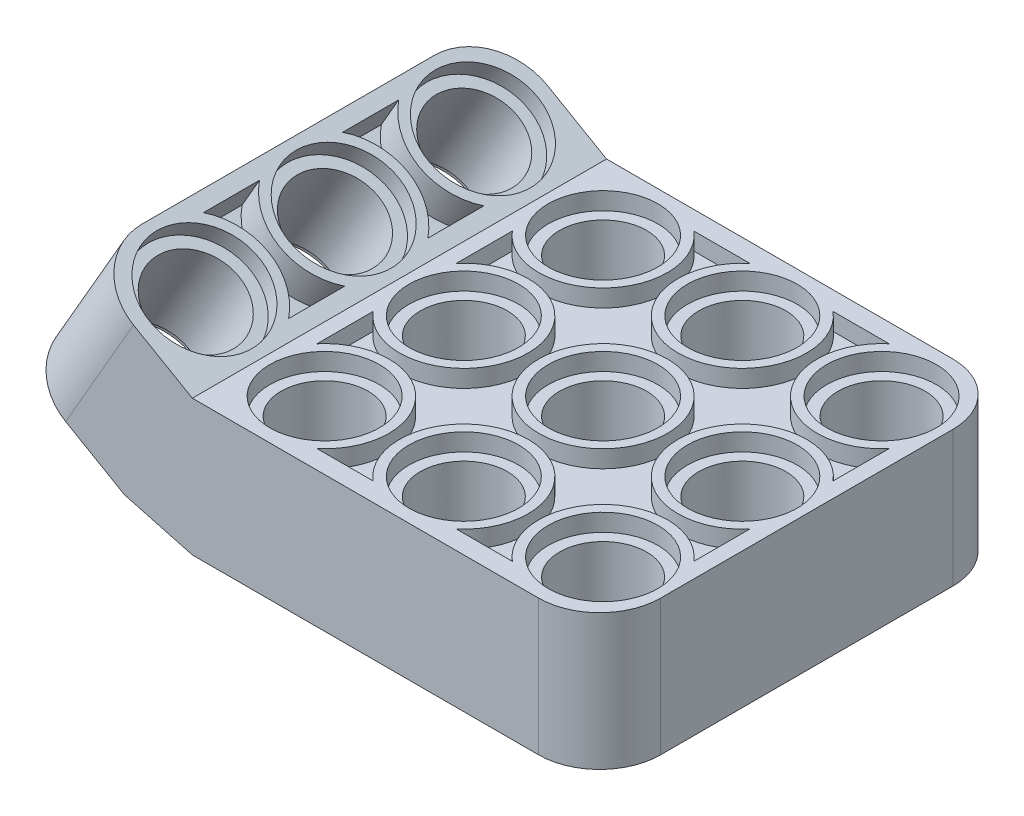
SolidWorks part; units mm, degrees
ref_plane "前视基准面" through (0, 0, 0) normal (0, 0, 1) x (1, 0, 0)
ref_plane "上视基准面" through (0, 0, 0) normal (0, 1, 0) x (1, 0, 0)
ref_plane "右视基准面" through (0, 0, 0) normal (1, 0, 0) x (0, 0, -1)
other "Configuration Table"
sketch "草图1" plane through (0, 0, 0) normal (0, 0, 1) x (1, 0, 0)
  line L6 (-10.3086, 4.745) -> (-3.9, 1.045)
  line L7 (-10.3086, 4.745) -> (-6.4086, 11.5)
  line L8 (-3.9, 1.045) -> (0, 7.8)
  line L9 (-6.4086, 11.5) -> (0, 7.8)
  line L11 (0, 7.8) -> (23.4, 7.8)
  line L12 (0, 7.8) -> (0, 0)
  line L13 (0, 0) -> (23.4, 0)
  line L14 (23.4, 7.8) -> (23.4, 0)
  line L16 (-3.9, 1.045) -> (0, 0)
  point P7 (-3.9, 0.7805)
  dimension "D1" = 7.8
  dimension "D2" = 7.8
  dimension "D3" = 150
  dimension "D4" = 23.4
  dimension "D5" = 7.4
extrude "凸台-拉伸1" add sketch "草图1" along normal blind 23.8 contours L9 L7 L6 L8 | L14 L11 L12 L13 | L8 L16 L12 region at (-5.1543, 6.2725, 0) region at (-1.3, 2.9483, 0) region at (11.7, 3.9, 0)
sketch "草图2" plane through (-0.5225, -0.905, 0) normal (-0.5, -0.866, 0) x (-0.866, 0.5, 0)
  line L0 (7.6, -23.8) -> (7.6, 0)
  line L1 (11.3, -23.8) -> (3.9, -23.8) construction
  line L2 (11.3, 0) -> (3.9, 0) construction
  line L3 (11.3, -11.9) -> (3.9, -11.9)
  line L4 (11.3, -23.8) -> (11.3, 0) construction
  line L5 (3.9, -23.8) -> (3.9, 0) construction
  line L7 (4.45, -11.9) -> (5.1, -11.9)
  circle A0 centre (7.6, -11.9) radius 2.5
  circle A1 centre (7.6, -11.9) radius 3.15
  circle A2 centre (7.6, -11.9) radius 3.7
  dimension "D1" = 7.4
  dimension "D2" = 6.3
  dimension "D3" = 5
extrude "切除-拉伸1" cut sketch "草图2" against normal up to next contours L0 A0 L3 | L3 A0 L0 | L0 A0 L3 | L3 A0 L0 region at (-6.1854, 2.3645, 12.961) region at (-8.0232, 3.4255, 12.961) region at (-6.1854, 2.3645, 10.839) region at (-8.0232, 3.4255, 10.839)
extrude "切除-拉伸2" cut sketch "草图2<3>" against normal blind 1 contours L0 A1 L3 A0 | L3 A1 L0 A0 | L0 A1 L3 A0 | L3 A1 L0 A0 region at (-5.5399, 1.9918, 13.7064) region at (-8.6687, 3.7982, 13.7064) region at (-5.5399, 1.9918, 10.0936) region at (-8.6687, 3.7982, 10.0936)
sketch "草图2<3>" plane through (-0.5225, -0.905, 0) normal (-0.5, -0.866, 0) x (-0.866, 0.5, 0) same geometry as "草图2"
extrude "切除-拉伸3" cut sketch "草图2<4>" along normal blind 1 from surface contours L0 A1 L3 A0 | L3 A1 L0 A0 | L0 A1 L3 A0 | L3 A1 L0 A0 region at (-5.5399, 1.9918, 13.7064) region at (-8.6687, 3.7982, 13.7064) region at (-5.5399, 1.9918, 10.0936) region at (-8.6687, 3.7982, 10.0936) starting at face at (-5.3694, 10.9, 11.9)
sketch "草图2<4>" plane through (-0.5225, -0.905, 0) normal (-0.5, -0.866, 0) x (-0.866, 0.5, 0) same geometry as "草图2"
pattern_linear "阵列(线性)1" count 2 spacing 8 along (0, 0, -1) count 2 spacing 8 along (0, 0, 1) of "切除-拉伸1", "切除-拉伸2", "切除-拉伸3"
sketch "草图4" plane through (-0.5225, -0.905, 0) normal (-0.5, -0.866, 0) x (0.866, -0.5, 0)
  line L0 (-7.6, 23.8) -> (-7.6, 0)
  line L1 (-11.3, 23.8) -> (-3.9, 23.8) construction
  line L2 (-11.3, 0) -> (-3.9, 0) construction
  line L3 (-11.3, 11.9) -> (-3.9, 11.9)
  line L4 (-11.3, 23.8) -> (-11.3, 0) construction
  line L5 (-3.9, 23.8) -> (-3.9, 0) construction
  line L6 (-10.75, 11.9) -> (-10.75, 3.9) construction
  line L7 (-10.75, 3.9) -> (-10.1, 3.9)
  line L8 (-10.1, 3.9) -> (-10.1, 11.9) construction
  line L9 (-5.1, 11.9) -> (-5.1, 3.9) construction
  line L10 (-5.1, 3.9) -> (-4.45, 3.9)
  line L11 (-4.45, 3.9) -> (-4.45, 11.9) construction
  line L12 (-10.425, 3.9) -> (-10.425, 11.9)
  line L13 (-4.775, 3.9) -> (-4.775, 11.9)
  circle A0 centre (-7.6, 11.9) radius 2.5
  circle A1 centre (-7.6, 11.9) radius 3.15
  circle A2 centre (-7.6, 11.9) radius 3.7
  circle A3 centre (-7.6, 3.9) radius 2.5
  circle A4 centre (-7.6, 3.9) radius 3.15
  circle A5 centre (-7.6, 3.9) radius 3.7
  dimension "D1" = 7.4
  dimension "D2" = 6.3
  dimension "D3" = 5
extrude "切除-拉伸4" cut sketch "草图4" against normal blind 2 contours A5 L0 A2 L12 | A5 L13 A2 L0 region at (-5.5178, 1.979, 7.9) region at (-8.6908, 3.811, 7.9)
extrude "切除-拉伸5" cut sketch "草图4<3>" along normal blind 2 from surface contours A5 L0 A2 L12 | A5 L13 A2 L0 region at (-5.5178, 1.979, 7.9) region at (-8.6908, 3.811, 7.9) starting at face at (-5.9323, 11.225, 19.9)
sketch "草图4<3>" plane through (-0.5225, -0.905, 0) normal (-0.5, -0.866, 0) x (0.866, -0.5, 0) same geometry as "草图4"
pattern_linear "阵列(线性)2" count 2 spacing 8 along (0, 0, 1) of "切除-拉伸4", "切除-拉伸5"
sketch "草图5" plane through (0, 0, 0) normal (0, -1, 0) x (1, 0, 0)
  line L0 (0, 11.9) -> (23.4, 11.9) construction
  line L1 (0, 23.8) -> (0, 0) construction
  line L2 (23.4, 23.8) -> (23.4, 0) construction
  line L3 (11.7, 23.8) -> (11.7, 0) construction
  line L4 (0, 23.8) -> (23.4, 23.8) construction
  line L5 (0, 0) -> (23.4, 0) construction
  line L6 (22.2, 11.9) -> (22.2, 19.9) construction
  line L7 (22.2, 19.9) -> (22.85, 19.9)
  line L8 (22.85, 19.9) -> (22.85, 11.9) construction
  line L9 (16.55, 11.9) -> (16.55, 19.9) construction
  line L10 (16.55, 19.9) -> (17.2, 19.9)
  line L11 (17.2, 19.9) -> (17.2, 11.9) construction
  line L12 (16.875, 19.9) -> (16.875, 14.2894)
  line L13 (22.525, 19.9) -> (22.525, 14.2894)
  line L14 (19.7, 22.725) -> (14.0894, 22.725)
  line L15 (19.7, 23.05) -> (19.7, 22.4)
  line L16 (19.7, 22.4) -> (11.7, 22.4) construction
  line L17 (11.7, 17.4) -> (19.7, 17.4) construction
  line L18 (19.7, 17.4) -> (19.7, 16.75)
  line L19 (19.7, 17.075) -> (14.0894, 17.075)
  circle A0 centre (11.7, 11.9) radius 2.5
  circle A1 centre (11.7, 11.9) radius 3.15
  circle A2 centre (11.7, 11.9) radius 3.7
  circle A3 centre (3.7, 11.9) radius 2.5
  circle A4 centre (3.7, 11.9) radius 3.15
  circle A5 centre (3.7, 11.9) radius 3.7
  circle A6 centre (19.7, 11.9) radius 3.15
  circle A7 centre (19.7, 11.9) radius 2.5
  circle A8 centre (19.7, 11.9) radius 3.7
  circle A9 centre (19.7, 19.9) radius 2.5
  circle A10 centre (19.7, 19.9) radius 3.15
  circle A11 centre (19.7, 19.9) radius 3.7
  circle A12 centre (11.7, 19.9) radius 2.5
  circle A13 centre (11.7, 19.9) radius 3.15
  circle A14 centre (11.7, 19.9) radius 3.7
  dimension "D1" = 7.4
  dimension "D2" = 6.3
  dimension "D3" = 5
  dimension "D4" = 8
  dimension "D5" = 8
  dimension "D6" = 8
extrude "切除-拉伸6" cut sketch "草图5" against normal up to next contours A0 | A7 | A3 region at (11.7, 0, 11.9) region at (3.7, 0, 11.9) region at (19.7, 0, 11.9)
extrude "切除-拉伸7" cut sketch "草图5<3>" against normal blind 1 contours A4 A3 | A6 A7 | A1 A0 region at (8.6391, 0, 11.9) region at (0.6391, 0, 11.9) region at (16.6391, 0, 11.9)
sketch "草图5<3>" plane through (0, 0, 0) normal (0, -1, 0) x (1, 0, 0) same geometry as "草图5"
extrude "切除-拉伸8" cut sketch "草图5<4>" along normal blind 1 from surface contours A1 A0 | A6 A7 | A4 A3 region at (8.6391, 0, 11.9) region at (0.6391, 0, 11.9) region at (16.6391, 0, 11.9) starting at face at (1.2, 7.8, 11.9)
sketch "草图5<4>" plane through (0, 0, 0) normal (0, -1, 0) x (1, 0, 0) same geometry as "草图5"
pattern_linear "阵列(线性)3" count 2 spacing 8 along (0, 0, -1) count 2 spacing 8 along (0, 0, 1) of "切除-拉伸6", "切除-拉伸7", "切除-拉伸8"
extrude "切除-拉伸10" cut sketch "草图5<6>" against normal blind 1 contours A14 L19 L12 A11 L14 | A11 L12 L19 region at (17.0161, 0, 17.2161) region at (15.6849, 0, 19.9307)
sketch "草图5<6>" plane through (0, 0, 0) normal (0, -1, 0) x (1, 0, 0) same geometry as "草图5"
extrude "切除-拉伸11" cut sketch "草图5<7>" along normal blind 1 from surface contours A14 L19 L12 A11 L14 | A11 L12 L19 region at (17.0161, 0, 17.2161) region at (15.6849, 0, 19.9307) starting at face at (16.55, 7.8, 19.9)
sketch "草图5<7>" plane through (0, 0, 0) normal (0, -1, 0) x (1, 0, 0) same geometry as "草图5"
pattern_linear "阵列(线性)4" count 2 spacing 8 along (-1, 0, 0) count 3 spacing 8 along (0, 0, -1) of "切除-拉伸10", "切除-拉伸11"
extrude "切除-拉伸12" cut sketch "草图5<8>" against normal blind 1 contours A11 L19 L12 A8 L13 | A11 L12 L19 region at (19.7307, 0, 15.8849) region at (17.0161, 0, 17.2161)
sketch "草图5<8>" plane through (0, 0, 0) normal (0, -1, 0) x (1, 0, 0) same geometry as "草图5"
extrude "切除-拉伸13" cut sketch "草图5<9>" along normal blind 1 from surface contours A11 L19 L12 A8 L13 | A11 L12 L19 region at (19.7307, 0, 15.8849) region at (17.0161, 0, 17.2161) starting at face at (15.7, 7.8, 3.9)
sketch "草图5<9>" plane through (0, 0, 0) normal (0, -1, 0) x (1, 0, 0) same geometry as "草图5"
pattern_linear "阵列(线性)5" count 3 spacing 8 along (-1, 0, 0) count 2 spacing 8 along (0, 0, -1) of "切除-拉伸13", "切除-拉伸12"
sketch "草图6" plane through (0, 7.8, 0) normal (0, 1, 0) x (1, 0, 0)
  line L0 (16.875, -6.725) -> (16.875, -9.075) construction
  line L1 (6.525, -6.725) -> (8.875, -6.725)
  line L2 (6.525, -6.725) -> (6.525, -9.075)
  line L3 (6.525, -9.075) -> (8.875, -9.075)
  line L4 (8.875, -6.725) -> (8.875, -9.075)
  line L5 (14.525, -6.725) -> (16.875, -6.725)
  line L6 (14.525, -6.725) -> (14.525, -9.075)
  line L7 (14.525, -9.075) -> (16.875, -9.075)
  line L8 (16.875, -6.725) -> (16.875, -9.075)
  line L9 (14.525, -9.075) -> (16.875, -9.075) construction
  line L10 (6.525, -17.075) -> (8.875, -17.075) construction
  line L11 (6.525, -14.725) -> (8.875, -14.725)
  line L12 (6.525, -14.725) -> (6.525, -17.075)
  line L13 (6.525, -17.075) -> (8.875, -17.075)
  line L14 (8.875, -14.725) -> (8.875, -17.075)
  line L16 (14.525, -14.725) -> (16.875, -14.725)
  line L17 (14.525, -14.725) -> (14.525, -17.075)
  line L18 (14.525, -17.075) -> (16.875, -17.075)
  line L19 (16.875, -14.725) -> (16.875, -17.075)
extrude "切除-拉伸14" cut sketch "草图6" against normal blind 1
extrude "切除-拉伸15" cut sketch "草图6<2>" along normal blind 1 from surface starting at face at (15.7, 0, 7.9)
sketch "草图6<2>" plane through (0, 7.8, 0) normal (0, 1, 0) x (1, 0, 0) same geometry as "草图6"
fillet "圆角1" radius 3.5 4 edges at (-8.3586, 8.1225, 23.8) (-8.3586, 8.1225, 0) (23.4, 3.9, 0) (23.4, 3.9, 23.8)
equation "\"3‘\"=10"
